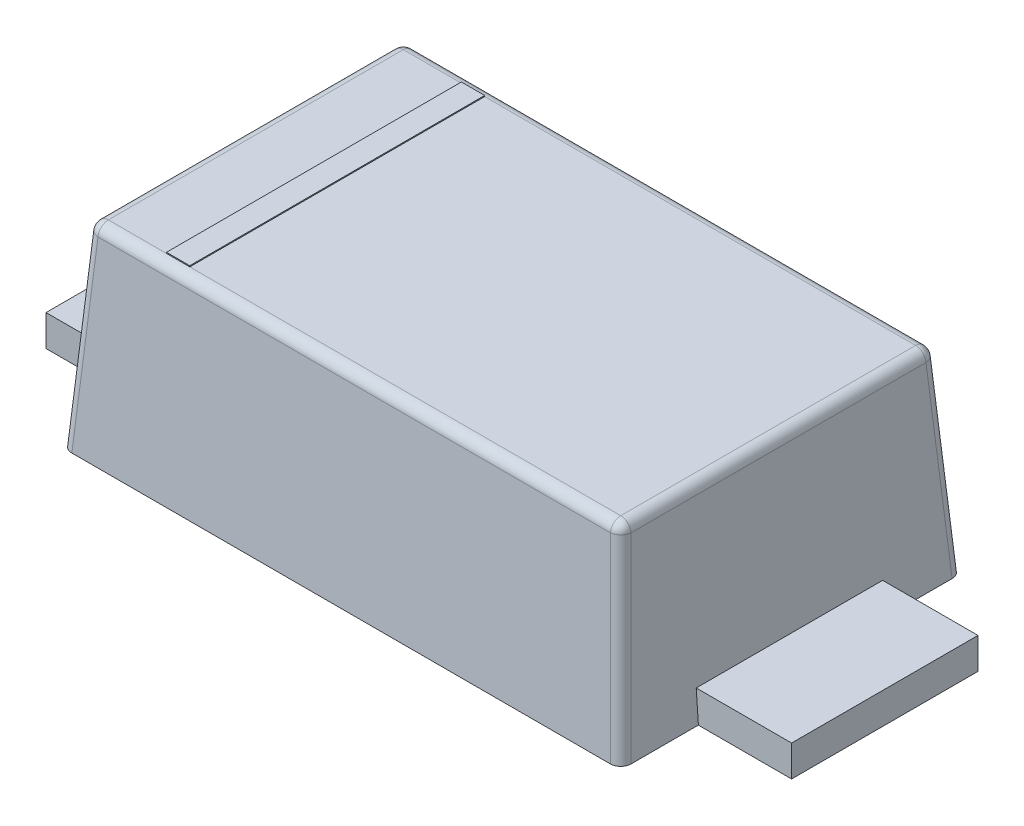
SolidWorks part; units mm, degrees
ref_plane "Front Plane" through (0, 0, 0) normal (0, 0, 1) x (1, 0, 0)
ref_plane "Top Plane" through (0, 0, 0) normal (0, 1, 0) x (1, 0, 0)
ref_plane "Right Plane" through (0, 0, 0) normal (1, 0, 0) x (0, 0, -1)
sketch "Sketch2" plane through (0, 0, 0) normal (0, 1, 0) x (1, 0, 0)
  line L1 (-1.35, -0.825) -> (1.35, -0.825)
  line L2 (-1.35, -0.825) -> (-1.35, 0.825)
  line L3 (-1.35, 0.825) -> (1.35, 0.825)
  line L4 (1.35, -0.825) -> (1.35, 0.825)
  line L5 (-1.35, -0.825) -> (1.35, 0.825) construction
  line L6 (-1.35, 0.825) -> (1.35, -0.825) construction
  point P0 (0, 0)
  dimension "D1" = 1.35
  dimension "D2" = 0.825
extrude "Boss-Extrude1" add sketch "Sketch2" along normal blind 0.95 draft 4 contours L3 L4 L1 L2
fillet "Fillet1" radius 0.05 8 edges at (-1.3168, 0.475, -0.7918) (-1.3168, 0.475, 0.7918) (1.3168, 0.475, 0.7918) (1.3168, 0.475, -0.7918) (0, 0.95, -0.7586) (1.2836, 0.95, 0) (0, 0.95, 0.7586) (-1.2836, 0.95, 0)
sketch "Sketch3" plane through (0, 0, 0) normal (0, -1, 0) x (1, 0, 0)
  line L0 (-1.35, 0.7751) -> (-1.35, -0.7751) construction
  line L1 (-1.3001, -0.825) -> (1.3001, -0.825) construction
  line L4 (-1.05, -0.45) -> (-1.8, 0.45) construction
  line L5 (-1.05, 0.45) -> (-1.8, -0.45) construction
  line L6 (1.05, -0.45) -> (1.8, -0.45)
  line L7 (1.05, -0.45) -> (1.05, 0.45)
  line L8 (1.05, 0.45) -> (1.8, 0.45)
  line L9 (1.8, -0.45) -> (1.8, 0.45)
  line L10 (1.05, -0.45) -> (1.8, 0.45) construction
  line L11 (1.05, 0.45) -> (1.8, -0.45) construction
  line L12 (-1.05, -0.45) -> (-1.05, 0.45)
  line L13 (-1.05, -0.45) -> (-1.8, -0.45)
  line L14 (-1.8, -0.45) -> (-1.8, 0.45)
  line L15 (-1.05, 0.45) -> (-1.8, 0.45)
  dimension "D1" = 0.3
  dimension "D2" = 2.4
  dimension "D3" = 3.15
  dimension "D4" = 0.375
  dimension "D5" = 1.275
extrude "Boss-Extrude2" add sketch "Sketch3" against normal blind 0.15
sketch "Sketch4" plane through (0, 0.95, 0) normal (0, 1, 0) x (1, 0, 0)
  line L0 (1.2369, -0.7119) -> (1.2369, 0.7119) construction
  line L1 (1.2369, 0.7119) -> (-1.2369, 0.7119) construction
  line L2 (-0.8438, -0.7119) -> (-0.9562, -0.7119)
  line L3 (-0.8438, -0.7119) -> (-0.8438, 0.7119)
  line L4 (-0.8438, 0.7119) -> (-0.9562, 0.7119)
  line L5 (-0.9562, -0.7119) -> (-0.9562, 0.7119)
  line L6 (-0.8438, -0.7119) -> (-0.9562, 0.7119) construction
  line L7 (-0.8438, 0.7119) -> (-0.9562, -0.7119) construction
  dimension "D1" = 2.0808
  dimension "D2" = 2.1931
  dimension "D3" = 1.4239
extrude "Boss-Extrude3" add sketch "Sketch4" along normal blind 0.005 contours L5 L4 L3 L2
extrude "Boss-Extrude4" add sketch "Sketch3<2>" along normal blind 0.0005
sketch "Sketch3<2>" plane through (0, 0, 0) normal (0, -1, 0) x (1, 0, 0) same geometry as "Sketch3"
